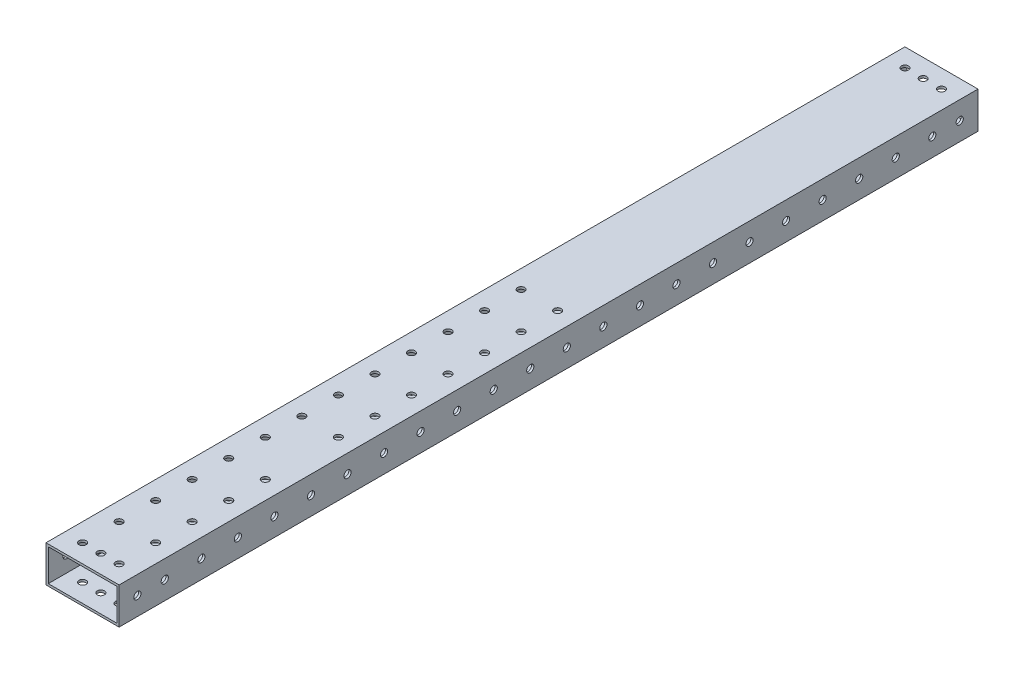
SolidWorks part; units mm, degrees
material "6061-T6 (SS)"
ref_plane "Front Plane" through (0, 0, 0) normal (0, 0, 1) x (1, 0, 0)
ref_plane "Top Plane" through (0, 0, 0) normal (0, 1, 0) x (1, 0, 0)
ref_plane "Right Plane" through (0, 0, 0) normal (1, 0, 0) x (0, 0, -1)
sketch "Sketch1" plane through (0, 0, 0) normal (0, 0, 1) x (1, 0, 0)
  line L1 (0, 0) -> (50.8, 0)
  line L2 (0, 0) -> (0, 25.4)
  line L3 (0, 25.4) -> (50.8, 25.4)
  line L4 (50.8, 0) -> (50.8, 25.4)
  dimension "D1" = 50.8
  dimension "D2" = 25.4
extrude "Boss-Extrude1" add sketch "Sketch1" along normal mid plane 596.9
shell "Shell1" thickness 1.5875 removed face at (25.4, 12.7, -298.45) removed face at (25.4, 12.7, 298.45)
sketch "Sketch2" plane through (0, 25.4, 0) normal (0, 1, 0) x (1, 0, 0)
  line L0 (50.8, -298.45) -> (50.8, 298.45) construction
  line L1 (50.8, -298.45) -> (0, -298.45) construction
  circle A0 centre (38.1, -285.75) radius 2.4892
  circle A1 centre (25.4, -285.75) radius 2.4892
  circle A2 centre (12.7, -285.75) radius 2.4892
  dimension "D1" = 4.9784
  dimension "D2" = 12.7
  dimension "D3" = 12.7
  dimension "D4" = 12.7
  dimension "D5" = 12.7
extrude "Cut-Extrude1" cut sketch "Sketch2" against normal through all
sketch "Sketch3" plane through (50.8, 0, 0) normal (1, 0, 0) x (0, 0, -1)
  line L0 (-298.45, 25.4) -> (298.45, 25.4) construction
  line L1 (-298.45, 0) -> (-298.45, 25.4) construction
  circle A0 centre (-285.75, 12.7) radius 2.4892
  dimension "D1" = 4.9784
  dimension "D2" = 12.7
  dimension "D3" = 12.7
extrude "Cut-Extrude2" cut sketch "Sketch3" against normal through all
mirror "Mirror1" about plane through (0, 0, 0) normal (0, 0, 1) of "Cut-Extrude1", "Cut-Extrude2"
sketch "Sketch4" plane through (50.8, 0, 0) normal (1, 0, 0) x (0, 0, -1)
  line L0 (-285.75, 12.7) -> (-266.7, 12.7) construction
  line L1 (-298.45, 0) -> (298.45, 0) construction
  line L2 (-298.45, 0) -> (-298.45, 25.4) construction
  circle A0 centre (-266.7, 12.7) radius 2.4892
  dimension "D1" = 4.9784
  dimension "D2" = 31.75
extrude "Cut-Extrude3" cut sketch "Sketch4" against normal through all and the other way through all
pattern_linear "LPattern1" count 22 spacing 25.4 along (0, 0, -1) of "Cut-Extrude3"
sketch "Sketch5" plane through (0, 0, 0) normal (0, -1, 0) x (1, 0, 0)
  circle A0 centre (12.7, 158.75) radius 2.4892 construction
  circle A1 centre (12.7, 184.15) radius 2.4892 construction
  circle A2 centre (38.1, 184.15) radius 2.4892 construction
  circle A3 centre (38.1, 209.55) radius 2.4892 construction
  circle A4 centre (12.7, 209.55) radius 2.4892 construction
  circle A5 centre (12.7, 234.95) radius 2.4892 construction
  circle A6 centre (38.1, 234.95) radius 2.4892 construction
  circle A7 centre (38.1, 260.35) radius 2.4892 construction
  circle A8 centre (12.7, 260.35) radius 2.4892 construction
  circle A9 centre (12.7, 158.75) radius 2.4892
  circle A10 centre (12.7, 184.15) radius 2.4892
  circle A11 centre (38.1, 184.15) radius 2.4892
  circle A12 centre (38.1, 209.55) radius 2.4892
  circle A13 centre (12.7, 209.55) radius 2.4892
  circle A14 centre (12.7, 234.95) radius 2.4892
  circle A15 centre (38.1, 234.95) radius 2.4892
  circle A16 centre (38.1, 260.35) radius 2.4892
  circle A17 centre (12.7, 260.35) radius 2.4892
  circle A18 centre (12.7, 31.75) radius 2.4892 construction
  circle A19 centre (38.1, 31.75) radius 2.4892 construction
  circle A20 centre (12.7, 57.15) radius 2.4892 construction
  circle A21 centre (38.1, 57.15) radius 2.4892 construction
  circle A22 centre (12.7, 82.55) radius 2.4892 construction
  circle A23 centre (38.1, 82.55) radius 2.4892 construction
  circle A24 centre (38.1, 107.95) radius 2.4892 construction
  circle A25 centre (38.1, 133.35) radius 2.4892 construction
  circle A26 centre (12.7, 107.95) radius 2.4892 construction
  circle A27 centre (12.7, 133.35) radius 2.4892 construction
  circle A28 centre (12.7, 31.75) radius 2.4892
  circle A29 centre (38.1, 31.75) radius 2.4892
  circle A30 centre (12.7, 57.15) radius 2.4892
  circle A31 centre (38.1, 57.15) radius 2.4892
  circle A32 centre (12.7, 82.55) radius 2.4892
  circle A33 centre (38.1, 82.55) radius 2.4892
  circle A34 centre (38.1, 107.95) radius 2.4892
  circle A35 centre (38.1, 133.35) radius 2.4892
  circle A36 centre (12.7, 107.95) radius 2.4892
  circle A37 centre (12.7, 133.35) radius 2.4892
  circle A38 centre (38.1, 6.35) radius 2.4892 construction
  circle A39 centre (38.1, -19.05) radius 2.4892 construction
  circle A40 centre (12.7, -19.05) radius 2.4892 construction
  circle A41 centre (12.7, 6.35) radius 2.4892 construction
  circle A42 centre (38.1, 6.35) radius 2.4892
  circle A43 centre (38.1, -19.05) radius 2.4892
  circle A44 centre (12.7, -19.05) radius 2.4892
  circle A45 centre (12.7, 6.35) radius 2.4892
extrude "Cut-Extrude4" cut sketch "Sketch5" against normal through all
